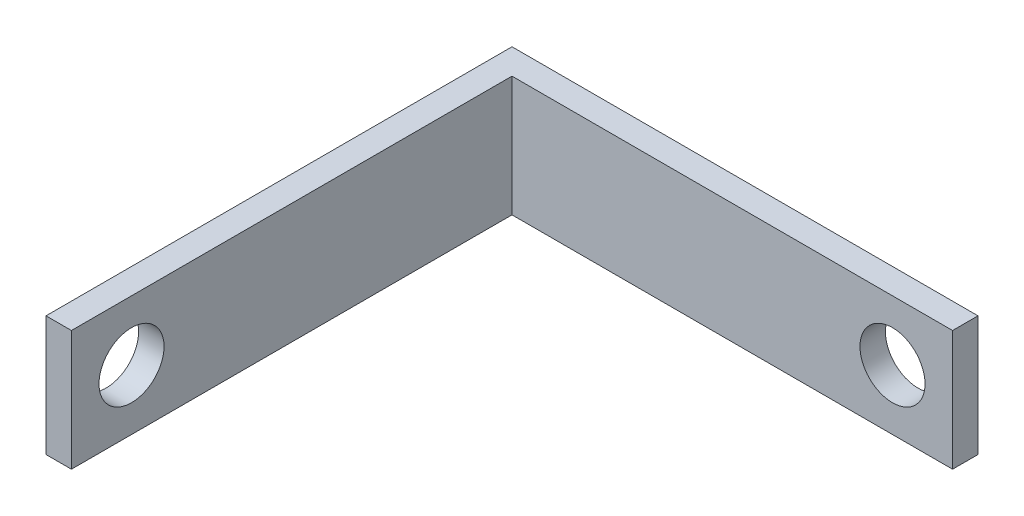
SolidWorks part; units mm, degrees
ref_plane "Front Plane" through (0, 0, 0) normal (0, 0, 1) x (1, 0, 0)
ref_plane "Top Plane" through (0, 0, 0) normal (0, 1, 0) x (1, 0, 0)
ref_plane "Right Plane" through (0, 0, 0) normal (1, 0, 0) x (0, 0, -1)
sketch "Sketch1" plane through (0, 0, 0) normal (0, 1, 0) x (1, 0, 0)
  line L0 (-24.5437, 0) -> (0, 0) construction
  line L1 (-3.75, 23.75) -> (3.75, 23.75)
  line L2 (-3.75, 23.75) -> (-3.75, 25.3375) construction
  line L3 (-3.75, 25.3375) -> (3.75, 25.3375)
  line L4 (3.75, 23.75) -> (3.75, 25.3375)
  line L5 (-3.75, 23.75) -> (3.75, 25.3375) construction
  line L6 (-3.75, 25.3375) -> (3.75, 23.75) construction
  line L7 (-25.3375, 3.75) -> (-23.75, 3.75) construction
  line L8 (-25.3375, 3.75) -> (-25.3375, -3.75)
  line L9 (-25.3375, -3.75) -> (-23.75, -3.75)
  line L10 (-23.75, 3.75) -> (-23.75, -3.75)
  line L11 (-25.3375, 3.75) -> (-23.75, -3.75) construction
  line L12 (-25.3375, -3.75) -> (-23.75, 3.75) construction
  line L13 (0, 0) -> (0, 24.5437) construction
  line L14 (-23.75, 3.75) -> (-23.75, 23.75)
  line L15 (-23.75, 23.75) -> (-3.75, 23.75)
  line L16 (-25.3375, 3.75) -> (-25.3375, 25.3375)
  line L17 (-25.3375, 25.3375) -> (-3.75, 25.3375)
  arc A0 (-23.75, 3.75) -> (-3.75, 23.75) centre (-3.75, 3.75) cw construction
  arc A1 (-25.3375, 3.75) -> (-3.75, 25.3375) centre (-3.75, 3.75) cw construction
  point P0 (0, 24.5437)
  point P5 (-24.5437, 0)
  point P16 (-23.75, 23.75)
  dimension "D3" = 20
  dimension "D1" = 1.5875
  dimension "D2" = 7.5
extrude "Boss-Extrude1" add sketch "Sketch1" along normal mid plane 7.5 contours L10 L7 L8 L9 | L1 L4 L3 L2 region at (-13.75, 0, -24.1614)
sketch "Sketch2" plane through (0, 0, -23.75) normal (0, 0, 1) x (1, 0, 0)
  circle A0 centre (0, 0) radius 2.03
  dimension "D1" = 4.06
extrude "Cut-Extrude1" cut sketch "Sketch2" against normal through all
sketch "Sketch3" plane through (-23.75, 0, 0) normal (1, 0, 0) x (0, 0, -1)
  circle A0 centre (0, 0) radius 2.03
  dimension "D1" = 4.06
extrude "Cut-Extrude2" cut sketch "Sketch3" against normal through all
